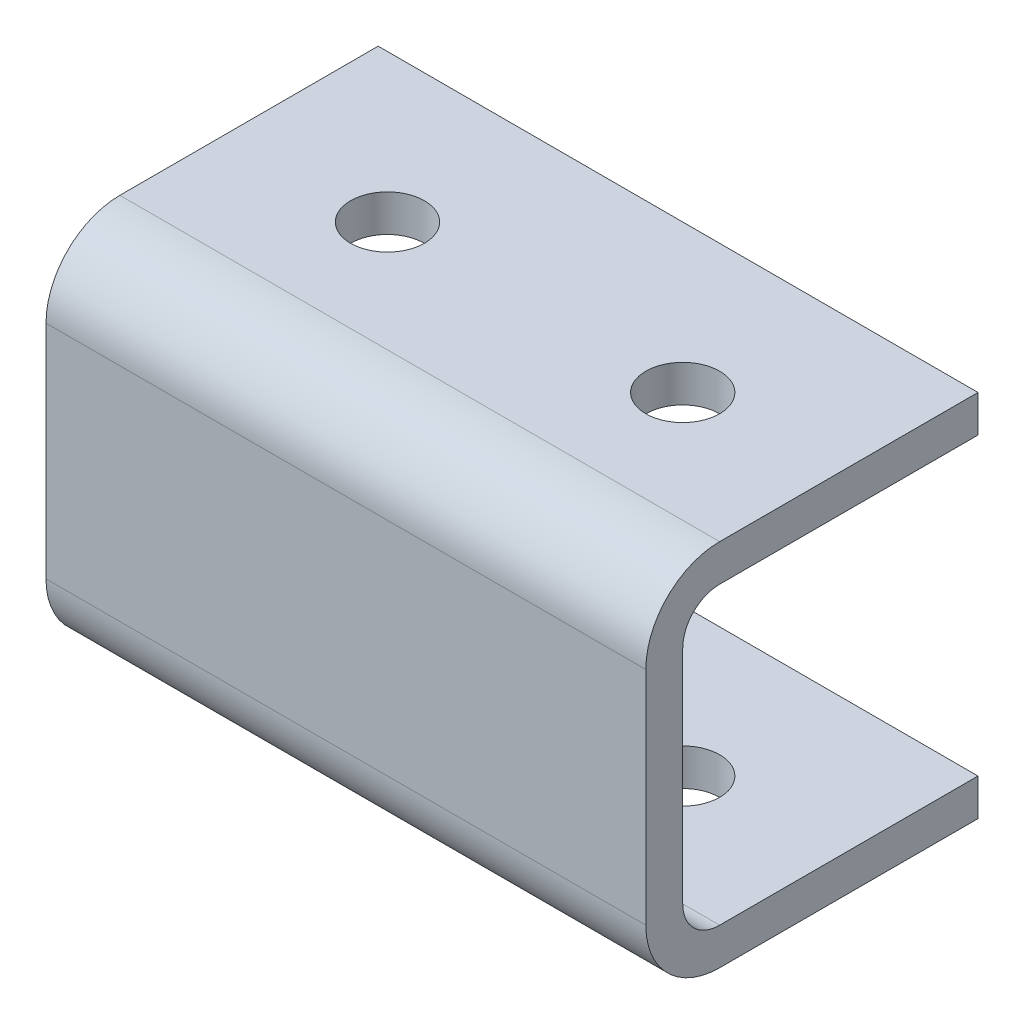
SolidWorks part; units mm, degrees
material "5052-O, Rod (SS)"
ref_plane "Front Plane" through (0, 0, 0) normal (0, 0, 1) x (1, 0, 0)
ref_plane "Top Plane" through (0, 0, 0) normal (0, 1, 0) x (1, 0, 0)
ref_plane "Right Plane" through (0, 0, 0) normal (1, 0, 0) x (0, 0, -1)
ref_plane "Plane1" through (0, 0, 3.175) normal (0, 0, 1) x (1, 0, 0)
sketch "Sketch1" plane through (0, 0, 3.175) normal (0, 0, 1) x (1, 0, 0)
  line L0 (872.98, -7.202) -> (872.98, 24.548)
  line L1 (872.98, 24.548) -> (-16.02, 24.548)
  line L2 (-16.02, 24.548) -> (-16.02, -7.202)
  line L3 (-16.02, -7.202) -> (872.98, -7.202)
extrude "Extrude1" add sketch "Sketch1" against normal blind 28.575
sketch "Sketch2" plane through (-16.02, 0, 0) normal (-1, 0, 0) x (0, 0, 1)
  line L0 (-25.4, 21.373) -> (-25.4, -4.027)
  line L1 (-25.4, -4.027) -> (0, -4.027)
  line L2 (0, -4.027) -> (0, 21.373)
  line L3 (0, 21.373) -> (-25.4, 21.373)
extrude "Extrude2" cut sketch "Sketch2" against normal up to next
hole_wizard "Hole1" positions "Sketch4" profile "Sketch3" legacy
sketch "Sketch4" plane through (0, 24.548, 0) normal (0, 1, 0) x (-1, 0, 0)
  point P0 (3.32, -12.7)
sketch "Sketch3" plane through (-3.32, 24.548, -12.7) normal (1, 0, 0) x (0, 0, 1)
  line L0 (0, 0) -> (0, 3.175)
  line L1 (0, 3.175) -> (3.175, 3.175)
  line L2 (3.175, 3.175) -> (3.175, 0)
  line L3 (3.175, 0) -> (0, 0)
  line L4 (0, 110) -> (0, -10) construction
  dimension "Diameter" = 6.35
  dimension "Depth" = 3.175
sketch3d "3DSketch1"
  point P0 (428.6664, 8.6668, -7.2024)
  point P1 (528.6664, 8.6668, -7.2024)
ref_axis "Axis1" through (528.6664, 8.6668, -7.2024) along (-1, 0, 0)
pattern_linear "LPattern1" count 35 spacing 25.4 along (1, 0, 0) of "Hole1"
hole_wizard "Hole2" positions "Sketch6" profile "Sketch5" legacy
sketch "Sketch6" plane through (0, 0, 3.175) normal (0, 0, 1) x (1, 0, 0)
  point P0 (66.53, 10.578)
sketch "Sketch5" plane through (66.53, 10.578, 3.175) normal (1, 0, 0) x (0, -1, 0)
  line L0 (0, 0) -> (0, 3.175)
  line L1 (0, 3.175) -> (4.826, 3.175)
  line L2 (4.826, 3.175) -> (4.826, 0)
  line L3 (4.826, 0) -> (0, 0)
  line L4 (0, 110) -> (0, -10) construction
  dimension "Diameter" = 9.652
  dimension "Depth" = 3.175
sketch3d "3DSketch2"
  point P0 (428.8468, 8.4517, -7.1294)
  point P1 (528.8468, 8.4517, -7.1294)
ref_axis "Axis2" through (528.8468, 8.4517, -7.1294) along (-1, 0, 0)
pattern_linear "LPattern2" count 12 spacing 25.4 along (1, 0, 0) skipping (2, 0), (3, 0), (4, 0), (5, 0), (6, 0), (7, 0), (8, 0), (9, 0) of "Hole2"
hole_wizard "Hole3" positions "Sketch8" profile "Sketch7" legacy
sketch "Sketch8" plane through (0, 0, 3.175) normal (0, 0, 1) x (1, 0, 0)
  point P0 (428.48, 6.768)
sketch "Sketch7" plane through (428.48, 6.768, 3.175) normal (1, 0, 0) x (0, -1, 0)
  line L0 (0, 0) -> (0, 3.175)
  line L1 (0, 3.175) -> (4.826, 3.175)
  line L2 (4.826, 3.175) -> (4.826, 0)
  line L3 (4.826, 0) -> (0, 0)
  line L4 (0, 110) -> (0, -10) construction
  dimension "Diameter" = 9.652
  dimension "Depth" = 3.175
hole_wizard "Hole4" positions "Sketch10" profile "Sketch9" legacy
sketch "Sketch10" plane through (0, 0, 3.175) normal (0, 0, 1) x (1, 0, 0)
  point P0 (511.03, 10.578)
sketch "Sketch9" plane through (511.03, 10.578, 3.175) normal (1, 0, 0) x (0, -1, 0)
  line L0 (0, 0) -> (0, 3.175)
  line L1 (0, 3.175) -> (4.826, 3.175)
  line L2 (4.826, 3.175) -> (4.826, 0)
  line L3 (4.826, 0) -> (0, 0)
  line L4 (0, 110) -> (0, -10) construction
  dimension "Diameter" = 9.652
  dimension "Depth" = 3.175
sketch3d "3DSketch3"
  point P0 (429.3014, 8.4448, -7.1738)
  point P1 (529.3014, 8.4448, -7.1738)
ref_axis "Axis3" through (529.3014, 8.4448, -7.1738) along (-1, 0, 0)
pattern_linear "LPattern3" count 12 spacing 25.4 along (1, 0, 0) skipping (2, 0), (3, 0), (4, 0), (5, 0), (6, 0), (7, 0), (8, 0), (9, 0) of "Hole4"
hole_wizard "Hole5" positions "Sketch12" profile "Sketch11" legacy
sketch "Sketch12" plane through (0, 0, 3.175) normal (0, 0, 1) x (1, 0, 0)
  point P0 (669.78, 8.673)
sketch "Sketch11" plane through (669.78, 8.673, 3.175) normal (1, 0, 0) x (0, -1, 0)
  line L0 (0, 0) -> (0, 3.175)
  line L1 (0, 3.175) -> (1.5875, 3.175)
  line L2 (1.5875, 3.175) -> (1.5875, 0)
  line L3 (1.5875, 0) -> (0, 0)
  line L4 (0, 110) -> (0, -10) construction
  dimension "Diameter" = 3.175
  dimension "Depth" = 3.175
hole_wizard "Hole6" positions "Sketch14" profile "Sketch13" legacy
sketch "Sketch14" plane through (0, -4.027, 0) normal (0, 1, 0) x (-1, 0, 0)
  point P0 (3.32, -12.7)
sketch "Sketch13" plane through (-3.32, -4.027, -12.7) normal (1, 0, 0) x (0, 0, 1)
  line L0 (0, 0) -> (0, 3.175)
  line L1 (0, 3.175) -> (3.175, 3.175)
  line L2 (3.175, 3.175) -> (3.175, 0)
  line L3 (3.175, 0) -> (0, 0)
  line L4 (0, 110) -> (0, -10) construction
  dimension "Diameter" = 6.35
  dimension "Depth" = 3.175
sketch3d "3DSketch4"
  point P0 (428.6444, 8.4444, -7.1991)
  point P1 (528.6444, 8.4444, -7.1991)
ref_axis "Axis4" through (528.6444, 8.4444, -7.1991) along (-1, 0, 0)
pattern_linear "LPattern4" count 35 spacing 25.4 along (1, 0, 0) of "Hole6"
fillet "Fillet1" radius 3.175 1 edges at (428.48, 21.373, 0) tangent propagation no
fillet "Fillet2" radius 3.175 1 edges at (428.48, -4.027, 0) tangent propagation no
fillet "Fillet3" radius 6.35 1 edges at (428.48, -7.202, 3.175) tangent propagation no
fillet "Fillet4" radius 6.35 1 edges at (428.48, 24.548, 3.175) tangent propagation no
ref_plane "Plane2" through (872.98, 24.548, -3.175) normal (1, 0, 0) x (0, 0, -1)
sketch "Sketch16" plane through (0, 24.548, 0) normal (0, 1, 0) x (1, 0, 0)
  line L0 (112.98, 3.175) -> (112.98, 25.4) construction
  line L1 (-16.02, 3.175) -> (872.98, 3.175) construction
  line L2 (872.98, 25.4) -> (-16.02, 25.4) construction
  line L3 (872.98, 25.4) -> (872.98, 3.175) construction
  line L6 (112.98, 3.175) -> (112.98, 25.4)
  line L7 (112.98, 25.4) -> (-16.02, 25.4)
  line L9 (112.98, 25.4) -> (-32.7801, 25.4)
  line L10 (112.98, 25.4) -> (112.98, -46.1048)
  line L11 (112.98, -46.1048) -> (-32.7801, -46.1048)
  line L12 (-32.7801, 25.4) -> (-32.7801, -46.1048)
  dimension "D1" = 760
extrude "Cut-Extrude2" cut sketch "Sketch16" against normal blind 75 contours L10 L11 L12 L9
sketch "Sketch17" plane through (0, 24.548, 0) normal (0, 1, 0) x (1, 0, 0)
  line L0 (524.98, 3.175) -> (524.98, 25.4) construction
  line L1 (112.98, 3.175) -> (872.98, 3.175) construction
  line L2 (872.98, 25.4) -> (112.98, 25.4) construction
  line L3 (872.98, 25.4) -> (872.98, 3.175) construction
  line L5 (524.98, 25.4) -> (51.3514, 25.4)
  line L6 (524.98, 25.4) -> (524.98, -41.5089)
  line L7 (524.98, -41.5089) -> (51.3514, -41.5089)
  line L8 (51.3514, 25.4) -> (51.3514, -41.5089)
  dimension "D1" = 348
extrude "Cut-Extrude3" cut sketch "Sketch17" against normal blind 186
sketch "Sketch18" plane through (0, 24.548, 0) normal (0, 1, 0) x (1, 0, 0)
  line L0 (812.98, 3.175) -> (812.98, 25.4) construction
  line L1 (524.98, 3.175) -> (872.98, 3.175) construction
  line L2 (872.98, 25.4) -> (524.98, 25.4) construction
  line L3 (872.98, 25.4) -> (872.98, 3.175) construction
  line L5 (812.98, 25.4) -> (429.8851, 25.4)
  line L6 (812.98, 25.4) -> (812.98, -68.5158)
  line L7 (812.98, -68.5158) -> (429.8851, -68.5158)
  line L8 (429.8851, 25.4) -> (429.8851, -68.5158)
  dimension "D1" = 60
extrude "Cut-Extrude4" cut sketch "Sketch18" against normal blind 186
sketch "Sketch19" plane through (0, 24.548, 0) normal (0, 1, 0) x (1, 0, 0)
  line L0 (821.38, 3.175) -> (821.38, 25.4) construction
  line L1 (812.98, 3.175) -> (872.98, 3.175) construction
  line L2 (872.98, 25.4) -> (812.98, 25.4) construction
  line L3 (872.98, 25.4) -> (872.98, 3.175) construction
  line L5 (821.38, 25.4) -> (777.0563, 25.4)
  line L6 (821.38, 25.4) -> (821.38, -28.3496)
  line L7 (821.38, -28.3496) -> (777.0563, -28.3496)
  line L8 (777.0563, 25.4) -> (777.0563, -28.3496)
  dimension "D1" = 51.6
extrude "Cut-Extrude5" cut sketch "Sketch19" against normal blind 186
